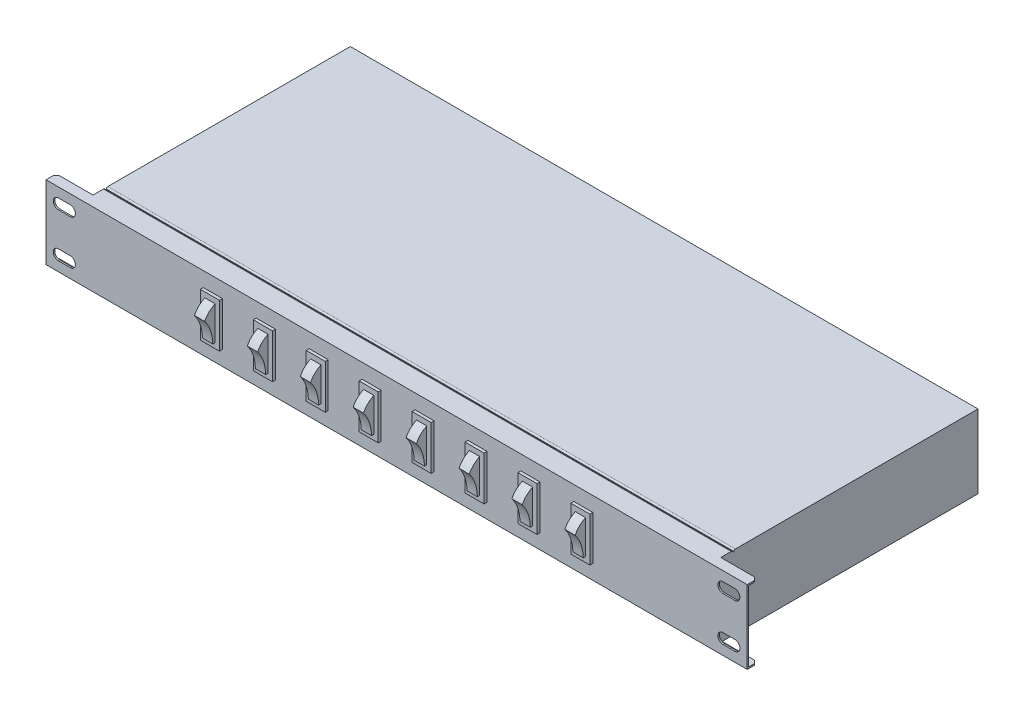
SolidWorks part; units mm, degrees
ref_plane "Front Plane" through (0, 0, 0) normal (0, 0, 1) x (1, 0, 0)
ref_plane "Top Plane" through (0, 0, 0) normal (0, 1, 0) x (1, 0, 0)
ref_plane "Right Plane" through (0, 0, 0) normal (1, 0, 0) x (0, 0, -1)
sketch "Sketch1" plane through (0, 0, 0) normal (0, 1, 0) x (1, 0, 0)
  line L1 (0, 0) -> (427, 0)
  line L2 (0, 0) -> (0, 182)
  line L3 (0, 182) -> (427, 182)
  line L4 (427, 0) -> (427, 182)
  dimension "D1" = 427
  dimension "D2" = 182
extrude "Boss-Extrude1" add sketch "Sketch1" along normal blind 50
sketch "Sketch2" plane through (0, 0, 0) normal (0, 0, 1) x (1, 0, 0)
  line L0 (18.7689, 0) -> (-75.6235, 0) construction
  line L1 (0, 0) -> (427, 0) construction
  line L2 (-16.5385, 40) -> (-8.5385, 40) construction
  line L3 (0, 50) -> (-25, 50)
  line L4 (0, 50) -> (0, 0)
  line L5 (0, 0) -> (-25, 0)
  line L6 (-25, 50) -> (-25, 0)
  line L7 (-16.5385, 43.5) -> (-8.5385, 43.5)
  line L8 (-16.5385, 36.5) -> (-8.5385, 36.5)
  line L9 (213.5, 50) -> (213.5, 0) construction
  line L10 (0, 50) -> (427, 50) construction
  line L11 (-25, 25) -> (0, 25) construction
  line L12 (-16.5385, 10) -> (-8.5385, 10) construction
  line L13 (-16.5385, 13.5) -> (-8.5385, 13.5)
  line L14 (-16.5385, 6.5) -> (-8.5385, 6.5)
  line L15 (427, 50) -> (452, 50)
  line L16 (427, 50) -> (427, 0)
  line L17 (452, 50) -> (452, 0)
  line L18 (427, 0) -> (452, 0)
  line L19 (443.5385, 10) -> (435.5385, 10) construction
  line L20 (443.5385, 6.5) -> (435.5385, 6.5)
  line L21 (443.5385, 13.5) -> (435.5385, 13.5)
  line L22 (443.5385, 40) -> (435.5385, 40) construction
  line L23 (443.5385, 36.5) -> (435.5385, 36.5)
  line L24 (443.5385, 43.5) -> (435.5385, 43.5)
  circle A0 centre (-16.5385, 40) radius 3.5
  circle A1 centre (-8.5385, 40) radius 3.5
  circle A2 centre (-8.5385, 10) radius 3.5
  circle A3 centre (-16.5385, 10) radius 3.5
  circle A4 centre (443.5385, 10) radius 3.5
  circle A5 centre (435.5385, 10) radius 3.5
  circle A6 centre (435.5385, 40) radius 3.5
  circle A7 centre (443.5385, 40) radius 3.5
  line M10 (427, 0) -> (427, 50)
  line M12 (0, 50) -> (0, 0)
  dimension "D3" = 10
  dimension "D1" = 25
  dimension "D2" = 8
extrude "Boss-Extrude2" add sketch "Sketch2" against normal blind 1 contours L3 L6 L5 A1 L8 A0 L7 L14 A3 L13 A2 M12 | L18 L17 L15 A5 L21 A4 L20 L24 A7 L23 A6 M10
sketch "Sketch3" plane through (0, 0, -1) normal (0, 0, -1) x (-1, 0, 0)
  line L0 (0, 50) -> (0, 0) construction
  line L1 (25, 0) -> (0, 0)
  line L2 (25, 0) -> (25, 1)
  line L3 (25, 1) -> (0, 1)
  line L4 (0, 0) -> (0, 1)
  line L5 (25, 50) -> (25, 0) construction
  line L6 (0, 50) -> (25, 50)
  line L7 (0, 50) -> (0, 49)
  line L8 (0, 49) -> (25, 49)
  line L9 (25, 50) -> (25, 49)
  line L10 (-452, 50) -> (-452, 0) construction
  line L11 (-427, 50) -> (-452, 50)
  line L12 (-427, 50) -> (-427, 49)
  line L13 (-427, 49) -> (-452, 49)
  line L14 (-452, 50) -> (-452, 49)
  line L16 (-427, 0) -> (-452, 0)
  line L17 (-427, 0) -> (-427, 1)
  line L18 (-427, 1) -> (-452, 1)
  line L19 (-452, 0) -> (-452, 1)
  dimension "D1" = 1
  dimension "D2" = 1
  dimension "D3" = 1
  dimension "D4" = 1
extrude "Boss-Extrude3" add sketch "Sketch3" along normal blind 6
chamfer "Chamfer1" distance 2 angle 45 4 edges at (-25, 0.5, -7) (-25, 49.5, -7) (452, 49.5, -7) (452, 0.5, -7)
sketch "Sketch4" plane through (0, 0, 0) normal (0, 0, 1) x (1, 0, 0)
  line L0 (-25, 0) -> (452, 0) construction
  line L1 (82, 40) -> (95, 40)
  line L2 (82, 40) -> (82, 10)
  line L3 (82, 10) -> (95, 10)
  line L4 (95, 40) -> (95, 10)
  line L5 (-25, 50) -> (-25, 0) construction
  line L6 (118, 10) -> (131, 10)
  line L7 (131, 40) -> (131, 10)
  line L8 (118, 40) -> (131, 40)
  line L9 (118, 40) -> (118, 10)
  line L10 (154, 10) -> (167, 10)
  line L11 (167, 40) -> (167, 10)
  line L12 (154, 40) -> (167, 40)
  line L13 (154, 40) -> (154, 10)
  line L14 (190, 10) -> (203, 10)
  line L15 (203, 40) -> (203, 10)
  line L16 (190, 40) -> (203, 40)
  line L17 (190, 40) -> (190, 10)
  line L18 (226, 10) -> (239, 10)
  line L19 (239, 40) -> (239, 10)
  line L20 (226, 40) -> (239, 40)
  line L21 (226, 40) -> (226, 10)
  line L22 (262, 10) -> (275, 10)
  line L23 (275, 40) -> (275, 10)
  line L24 (262, 40) -> (275, 40)
  line L25 (262, 40) -> (262, 10)
  line L26 (298, 10) -> (311, 10)
  line L27 (311, 40) -> (311, 10)
  line L28 (298, 40) -> (311, 40)
  line L29 (298, 40) -> (298, 10)
  line L30 (334, 10) -> (347, 10)
  line L31 (347, 40) -> (347, 10)
  line L32 (334, 40) -> (347, 40)
  line L33 (334, 40) -> (334, 10)
  dimension "D1" = 30
  dimension "D2" = 13
  dimension "D3" = 10
  dimension "D4" = 107
  dimension "D5" = 8
extrude "Boss-Extrude4" add sketch "Sketch4" along normal blind 2
sketch "Sketch5" plane through (0, 0, 2) normal (0, 0, 1) x (1, 0, 0)
  line L0 (88.5, 36.5) -> (88.5, 13.5) construction
  line L1 (85, 36.5) -> (92, 36.5)
  line L2 (85, 36.5) -> (85, 13.5)
  line L3 (85, 13.5) -> (92, 13.5)
  line L4 (92, 36.5) -> (92, 13.5)
  line L5 (82, 10) -> (95, 10) construction
  line L6 (82, 40) -> (82, 10) construction
  line L7 (128, 36.5) -> (128, 13.5)
  line L8 (121, 36.5) -> (121, 13.5)
  line L9 (121, 36.5) -> (128, 36.5)
  line L10 (121, 13.5) -> (128, 13.5)
  line L11 (164, 36.5) -> (164, 13.5)
  line L12 (157, 36.5) -> (157, 13.5)
  line L13 (157, 36.5) -> (164, 36.5)
  line L14 (157, 13.5) -> (164, 13.5)
  line L15 (200, 36.5) -> (200, 13.5)
  line L16 (193, 36.5) -> (193, 13.5)
  line L17 (193, 36.5) -> (200, 36.5)
  line L18 (193, 13.5) -> (200, 13.5)
  line L19 (236, 36.5) -> (236, 13.5)
  line L20 (229, 36.5) -> (229, 13.5)
  line L21 (229, 36.5) -> (236, 36.5)
  line L22 (229, 13.5) -> (236, 13.5)
  line L23 (272, 36.5) -> (272, 13.5)
  line L24 (265, 36.5) -> (265, 13.5)
  line L25 (265, 36.5) -> (272, 36.5)
  line L26 (265, 13.5) -> (272, 13.5)
  line L27 (308, 36.5) -> (308, 13.5)
  line L28 (301, 36.5) -> (301, 13.5)
  line L29 (301, 36.5) -> (308, 36.5)
  line L30 (301, 13.5) -> (308, 13.5)
  line L31 (344, 36.5) -> (344, 13.5)
  line L32 (337, 36.5) -> (337, 13.5)
  line L33 (337, 36.5) -> (344, 36.5)
  line L34 (337, 13.5) -> (344, 13.5)
  point P6 (88.5, 25)
  dimension "D1" = 7
  dimension "D2" = 23
  dimension "D3" = 15
  dimension "D4" = 6.5
  dimension "D5" = 8
extrude "Boss-Extrude5" add sketch "Sketch5" along normal blind 7
sketch "Sketch6" plane through (85, 0, 0) normal (-1, 0, 0) x (0, 0, 1)
  line L0 (9, 36.5) -> (9, 29.5) construction
  line L1 (9, 36.5) -> (9, 13.5) construction
  line L2 (2, 13.5) -> (3.5, 13.5)
  line L3 (9, 13.5) -> (2, 13.5) construction
  line L4 (2, 36.5) -> (2, 13.5)
  line L5 (9, 36.5) -> (9, 29.5)
  line L6 (2, 36.5) -> (9, 36.5)
  line L7 (3.5, 13.5) -> (9, 13.5)
  line L8 (9, 13.5) -> (9, 29.5)
  line L9 (9, 29.5) -> (8.9442, 29.6581)
  spline S0 degree 2 poles (2, 36.5) (7.2388, 33.7202) (9, 29.5) knots 0 0 0 0.496809 0.496809 0.496809
  spline S1 degree 2 poles (3.5, 13.5) (3.8992, 22.9335) (9, 29.5) knots 0 0 0 0.757593 0.757593 0.757593
  dimension "D1" = 7
  dimension "D2" = 1.5
extrude "Cut-Extrude1" cut sketch "Sketch6" against normal blind 267
sketch "Sketch7" plane through (0, 50, 0) normal (0, 1, 0) x (1, 0, 0)
  line L0 (0, 182) -> (0, 7) construction
  line L1 (0, 16) -> (427, 16)
  line L2 (0, 16) -> (0, 15)
  line L3 (0, 15) -> (427, 15)
  line L4 (427, 16) -> (427, 15)
  line L5 (427, 7) -> (427, 182) construction
  line L6 (-25, 0) -> (452, 0) construction
  dimension "D1" = 15
  dimension "D2" = 1
extrude "Cut-Extrude2" cut sketch "Sketch7" against normal blind 1
sketch "Sketch8" plane through (0, 0, 0) normal (0, -1, 0) x (1, 0, 0)
  line L0 (427, -7) -> (427, -182) construction
  line L1 (427, -16) -> (0, -16)
  line L2 (427, -16) -> (427, -15)
  line L3 (427, -15) -> (0, -15)
  line L4 (0, -16) -> (0, -15)
  line L5 (0, -182) -> (0, -7) construction
  line L6 (-25, 0) -> (452, 0) construction
  dimension "D1" = 15
  dimension "D2" = 1
extrude "Cut-Extrude3" cut sketch "Sketch8" against normal blind 1
fillet "Fillet1" radius 1 12 edges at (0, 49.5, -15) (0, 49.5, -16) (427, 49.5, -16) (427, 49.5, -15) (213.5, 50, -15) (213.5, 50, -16) (427, 0.5, -15) (427, 0.5, -16) (0, 0.5, -16) (0, 0.5, -15) (213.5, 0, -15) (213.5, 0, -16)
sketch "Sketch9" plane through (0, 0, -182) normal (0, 0, -1) x (-1, 0, 0)
  line L0 (-383, 25) -> (-354, 25) construction
  line L1 (-383, 38) -> (-354, 38)
  line L2 (-383, 38) -> (-383, 12)
  line L3 (-383, 12) -> (-354, 12)
  line L4 (-354, 38) -> (-354, 12)
  line L5 (-427, 0) -> (0, 0) construction
  line L6 (-427, 1) -> (-427, 49) construction
  line L7 (-343, 38) -> (-314, 38)
  line L8 (-343, 38) -> (-343, 12)
  line L9 (-343, 12) -> (-314, 12)
  line L10 (-314, 38) -> (-314, 12)
  line L11 (-303, 38) -> (-274, 38)
  line L12 (-303, 38) -> (-303, 12)
  line L13 (-303, 12) -> (-274, 12)
  line L14 (-274, 38) -> (-274, 12)
  line L15 (-263, 38) -> (-234, 38)
  line L16 (-263, 38) -> (-263, 12)
  line L17 (-263, 12) -> (-234, 12)
  line L18 (-234, 38) -> (-234, 12)
  line L19 (-223, 38) -> (-194, 38)
  line L20 (-223, 38) -> (-223, 12)
  line L21 (-223, 12) -> (-194, 12)
  line L22 (-194, 38) -> (-194, 12)
  line L23 (-183, 38) -> (-154, 38)
  line L24 (-183, 38) -> (-183, 12)
  line L25 (-183, 12) -> (-154, 12)
  line L26 (-154, 38) -> (-154, 12)
  line L27 (-143, 38) -> (-114, 38)
  line L28 (-143, 38) -> (-143, 12)
  line L29 (-143, 12) -> (-114, 12)
  line L30 (-114, 38) -> (-114, 12)
  line L31 (-103, 38) -> (-74, 38)
  line L32 (-103, 38) -> (-103, 12)
  line L33 (-103, 12) -> (-74, 12)
  line L34 (-74, 38) -> (-74, 12)
  dimension "D1" = 29
  dimension "D2" = 26
  dimension "D3" = 25
  dimension "D4" = 44
  dimension "D5" = 8
extrude "Boss-Extrude6" add sketch "Sketch9" along normal blind 4
sketch "Sketch10" plane through (0, 0, -186) normal (0, 0, -1) x (-1, 0, 0)
  line L0 (-375.6, 29.9) -> (-361.8648, 29.9) construction
  line L1 (-375.6, 33.075) -> (-374.1, 33.075)
  line L2 (-375.6, 33.075) -> (-375.6, 26.725)
  line L3 (-375.6, 26.725) -> (-374.1, 26.725)
  line L4 (-374.1, 33.075) -> (-374.1, 26.725)
  line L5 (-362.9, 33.075) -> (-361.4, 33.075)
  line L6 (-362.9, 33.075) -> (-362.9, 26.725)
  line L7 (-362.9, 26.725) -> (-361.4, 26.725)
  line L8 (-361.4, 33.075) -> (-361.4, 26.725)
  line L9 (-383, 12) -> (-354, 12) construction
  line L10 (-383, 38) -> (-383, 12) construction
  line L11 (-322.9, 33.075) -> (-322.9, 26.725)
  line L12 (-322.9, 33.075) -> (-321.4, 33.075)
  line L13 (-321.4, 33.075) -> (-321.4, 26.725)
  line L14 (-322.9, 26.725) -> (-321.4, 26.725)
  line L15 (-335.6, 26.725) -> (-334.1, 26.725)
  line L16 (-334.1, 33.075) -> (-334.1, 26.725)
  line L17 (-335.6, 33.075) -> (-335.6, 26.725)
  line L18 (-335.6, 33.075) -> (-334.1, 33.075)
  line L19 (-282.9, 33.075) -> (-282.9, 26.725)
  line L20 (-282.9, 33.075) -> (-281.4, 33.075)
  line L21 (-281.4, 33.075) -> (-281.4, 26.725)
  line L22 (-282.9, 26.725) -> (-281.4, 26.725)
  line L23 (-295.6, 26.725) -> (-294.1, 26.725)
  line L24 (-294.1, 33.075) -> (-294.1, 26.725)
  line L25 (-295.6, 33.075) -> (-295.6, 26.725)
  line L26 (-295.6, 33.075) -> (-294.1, 33.075)
  line L27 (-242.9, 33.075) -> (-242.9, 26.725)
  line L28 (-242.9, 33.075) -> (-241.4, 33.075)
  line L29 (-241.4, 33.075) -> (-241.4, 26.725)
  line L30 (-242.9, 26.725) -> (-241.4, 26.725)
  line L31 (-255.6, 26.725) -> (-254.1, 26.725)
  line L32 (-254.1, 33.075) -> (-254.1, 26.725)
  line L33 (-255.6, 33.075) -> (-255.6, 26.725)
  line L34 (-255.6, 33.075) -> (-254.1, 33.075)
  line L35 (-202.9, 33.075) -> (-202.9, 26.725)
  line L36 (-202.9, 33.075) -> (-201.4, 33.075)
  line L37 (-201.4, 33.075) -> (-201.4, 26.725)
  line L38 (-202.9, 26.725) -> (-201.4, 26.725)
  line L39 (-215.6, 26.725) -> (-214.1, 26.725)
  line L40 (-214.1, 33.075) -> (-214.1, 26.725)
  line L41 (-215.6, 33.075) -> (-215.6, 26.725)
  line L42 (-215.6, 33.075) -> (-214.1, 33.075)
  line L43 (-162.9, 33.075) -> (-162.9, 26.725)
  line L44 (-162.9, 33.075) -> (-161.4, 33.075)
  line L45 (-161.4, 33.075) -> (-161.4, 26.725)
  line L46 (-162.9, 26.725) -> (-161.4, 26.725)
  line L47 (-175.6, 26.725) -> (-174.1, 26.725)
  line L48 (-174.1, 33.075) -> (-174.1, 26.725)
  line L49 (-175.6, 33.075) -> (-175.6, 26.725)
  line L50 (-175.6, 33.075) -> (-174.1, 33.075)
  line L51 (-122.9, 33.075) -> (-122.9, 26.725)
  line L52 (-122.9, 33.075) -> (-121.4, 33.075)
  line L53 (-121.4, 33.075) -> (-121.4, 26.725)
  line L54 (-122.9, 26.725) -> (-121.4, 26.725)
  line L55 (-135.6, 26.725) -> (-134.1, 26.725)
  line L56 (-134.1, 33.075) -> (-134.1, 26.725)
  line L57 (-135.6, 33.075) -> (-135.6, 26.725)
  line L58 (-135.6, 33.075) -> (-134.1, 33.075)
  line L59 (-82.9, 33.075) -> (-82.9, 26.725)
  line L60 (-82.9, 33.075) -> (-81.4, 33.075)
  line L61 (-81.4, 33.075) -> (-81.4, 26.725)
  line L62 (-82.9, 26.725) -> (-81.4, 26.725)
  line L63 (-95.6, 26.725) -> (-94.1, 26.725)
  line L64 (-94.1, 33.075) -> (-94.1, 26.725)
  line L65 (-95.6, 33.075) -> (-95.6, 26.725)
  line L66 (-95.6, 33.075) -> (-94.1, 33.075)
  circle A0 centre (-368.5, 18) radius 2.375
  circle A1 centre (-328.5, 18) radius 2.375
  circle A2 centre (-288.5, 18) radius 2.375
  circle A3 centre (-248.5, 18) radius 2.375
  circle A4 centre (-208.5, 18) radius 2.375
  circle A5 centre (-168.5, 18) radius 2.375
  circle A6 centre (-128.5, 18) radius 2.375
  circle A7 centre (-88.5, 18) radius 2.375
  point P12 (-362.9, 29.9)
  point P17 (-374.85, 33.075)
  point P18 (-362.15, 33.075)
  dimension "D1" = 4.75
  dimension "D2" = 6.35
  dimension "D3" = 6.35
  dimension "D4" = 1.5
  dimension "D5" = 1.5
  dimension "D6" = 11.9
  dimension "D7" = 0
  dimension "D8" = 6
  dimension "D9" = 14.5
  dimension "D10" = 12.7
  dimension "D11" = 6.35
  dimension "D12" = 8
extrude "Cut-Extrude4" cut sketch "Sketch10" against normal blind 15
chamfer "Chamfer2" distance 1 angle 45 72 edges at (362.9, 29.9, -186) (362.15, 33.075, -186) (361.4, 29.9, -186) (362.15, 26.725, -186) (374.85, 26.725, -186) (375.6, 29.9, -186) (374.85, 33.075, -186) (374.1, 29.9, -186) (366.125, 18, -186) (94.85, 26.725, -186) (94.1, 29.9, -186) (94.85, 33.075, -186) (95.6, 29.9, -186) (81.4, 29.9, -186) (82.15, 26.725, -186) (82.9, 29.9, -186) (82.15, 33.075, -186) (122.15, 26.725, -186) (121.4, 29.9, -186) (122.15, 33.075, -186) (122.9, 29.9, -186) (134.85, 26.725, -186) (134.1, 29.9, -186) (134.85, 33.075, -186) (135.6, 29.9, -186) (162.15, 26.725, -186) (161.4, 29.9, -186) (162.15, 33.075, -186) (162.9, 29.9, -186) (174.85, 26.725, -186) (174.1, 29.9, -186) (175.6, 29.9, -186) (174.85, 33.075, -186) (86.125, 18, -186) (126.125, 18, -186) (166.125, 18, -186) (206.125, 18, -186) (202.15, 26.725, -186) (201.4, 29.9, -186) (202.15, 33.075, -186) (202.9, 29.9, -186) (215.6, 29.9, -186) (214.85, 33.075, -186) (214.1, 29.9, -186) (214.85, 26.725, -186) (246.125, 18, -186) (242.15, 26.725, -186) (241.4, 29.9, -186) (242.15, 33.075, -186) (242.9, 29.9, -186) (255.6, 29.9, -186) (254.85, 33.075, -186) (254.1, 29.9, -186) (254.85, 26.725, -186) (282.15, 26.725, -186) (281.4, 29.9, -186) (282.15, 33.075, -186) (282.9, 29.9, -186) (286.125, 18, -186) (294.1, 29.9, -186) (294.85, 26.725, -186) (295.6, 29.9, -186) (294.85, 33.075, -186) (335.6, 29.9, -186) (334.85, 33.075, -186) (334.1, 29.9, -186) (334.85, 26.725, -186) (322.15, 26.725, -186) (321.4, 29.9, -186) (322.15, 33.075, -186) (322.9, 29.9, -186) (326.125, 18, -186)
sketch "Sketch11" plane through (0, 0, -182) normal (0, 0, -1) x (-1, 0, 0)
  line L0 (-427, 0) -> (0, 0) construction
  line L1 (-17.5363, 40.5) -> (-42.5363, 40.5)
  line L2 (-15.5363, 38.5) -> (-15.5363, 11.5)
  line L3 (-17.5363, 9.5) -> (-42.5363, 9.5)
  line L4 (-44.5363, 38.5) -> (-44.5363, 11.5)
  arc A0 (-17.5363, 40.5) -> (-15.5363, 38.5) centre (-17.5363, 38.5) cw
  arc A1 (-15.5363, 11.5) -> (-17.5363, 9.5) centre (-17.5363, 11.5) cw
  arc A2 (-42.5363, 9.5) -> (-44.5363, 11.5) centre (-42.5363, 11.5) cw
  arc A3 (-44.5363, 38.5) -> (-42.5363, 40.5) centre (-42.5363, 38.5) cw
  point P10 (-15.5363, 9.5)
  point P13 (-44.5363, 9.5)
  point P16 (-44.5363, 40.5)
  dimension "D4" = 2
  dimension "D1" = 29
  dimension "D2" = 31
  dimension "D3" = 9.5
extrude "Boss-Extrude7" add sketch "Sketch11" along normal blind 3.5
sketch "Sketch12" plane through (0, 0, -185.5) normal (0, 0, -1) x (-1, 0, 0)
  line L8 (-17.5363, 39.5) -> (-42.5363, 39.5)
  line L9 (-43.5363, 38.5) -> (-43.5363, 11.5)
  line L10 (-42.5363, 10.5) -> (-17.5363, 10.5)
  line L11 (-16.5363, 11.5) -> (-16.5363, 38.5)
  line L12 (-17.5363, 39.5) -> (-42.5363, 39.5)
  line L13 (-43.5363, 38.5) -> (-43.5363, 11.5)
  line L14 (-42.5363, 10.5) -> (-17.5363, 10.5)
  line L15 (-16.5363, 11.5) -> (-16.5363, 38.5)
  arc A8 (-16.5363, 38.5) -> (-17.5363, 39.5) centre (-17.5363, 38.5) ccw
  arc A9 (-42.5363, 39.5) -> (-43.5363, 38.5) centre (-42.5363, 38.5) ccw
  arc A10 (-43.5363, 11.5) -> (-42.5363, 10.5) centre (-42.5363, 11.5) ccw
  arc A11 (-17.5363, 10.5) -> (-16.5363, 11.5) centre (-17.5363, 11.5) ccw
  arc A12 (-16.5363, 38.5) -> (-17.5363, 39.5) centre (-17.5363, 38.5) ccw
  arc A13 (-42.5363, 39.5) -> (-43.5363, 38.5) centre (-42.5363, 38.5) ccw
  arc A14 (-43.5363, 11.5) -> (-42.5363, 10.5) centre (-42.5363, 11.5) ccw
  arc A15 (-17.5363, 10.5) -> (-16.5363, 11.5) centre (-17.5363, 11.5) ccw
  dimension "D1" = 1
extrude "Boss-Extrude8" add sketch "Sketch12" along normal blind 1.5
sketch "Sketch13" plane through (0, 0, -187) normal (0, 0, -1) x (-1, 0, 0)
  line L0 (-43.5363, 38.5) -> (-43.5363, 11.5) construction
  line L1 (-42.0363, 21.5) -> (-18.0363, 21.5)
  line L2 (-42.0363, 21.5) -> (-42.0363, 33.5)
  line L3 (-42.0363, 33.5) -> (-18.0363, 33.5)
  line L4 (-18.0363, 21.5) -> (-18.0363, 33.5)
  line L5 (-42.0363, 33.5) -> (-38.0363, 37.5)
  line L6 (-38.0363, 33.5) -> (-22.0363, 33.5)
  line L7 (-38.0363, 33.5) -> (-38.0363, 37.5)
  line L8 (-38.0363, 37.5) -> (-22.0363, 37.5)
  line L9 (-22.0363, 33.5) -> (-22.0363, 37.5)
  line L10 (-22.0363, 37.5) -> (-18.0363, 33.5)
  line L11 (-17.5363, 39.5) -> (-42.5363, 39.5) construction
  dimension "D1" = 24
  dimension "D2" = 1.5
  dimension "D3" = 12
  dimension "D4" = 4
  dimension "D5" = 4
  dimension "D6" = 16
  dimension "D7" = 2
extrude "Cut-Extrude5" cut sketch "Sketch13" against normal blind 15 contours L1 L4 L3 L2 | L3 L7 L5 | L3 L9 L8 L7 | L10 L9 L3
sketch "Sketch14" plane through (0, 0, -172) normal (0, 0, -1) x (-1, 0, 0)
  line L0 (-36.5363, 27.69) -> (-23.0363, 27.69) construction
  line L1 (-38.0363, 29.19) -> (-36.5363, 29.19)
  line L2 (-38.0363, 29.19) -> (-38.0363, 26.19)
  line L3 (-38.0363, 26.19) -> (-36.5363, 26.19)
  line L4 (-36.5363, 29.19) -> (-36.5363, 26.19)
  line L5 (-23.0363, 29.19) -> (-21.5363, 29.19)
  line L6 (-23.0363, 29.19) -> (-23.0363, 26.19)
  line L7 (-23.0363, 26.19) -> (-21.5363, 26.19)
  line L8 (-21.5363, 29.19) -> (-21.5363, 26.19)
  line L9 (-30.7863, 34.19) -> (-29.2863, 34.19)
  line L10 (-30.7863, 34.19) -> (-30.7863, 31.19)
  line L11 (-30.7863, 31.19) -> (-29.2863, 31.19)
  line L12 (-29.2863, 34.19) -> (-29.2863, 31.19)
  line L13 (-42.0363, 21.5) -> (-42.0363, 33.5) construction
  point P14 (-30.7863, 32.69)
  point P15 (-37.2863, 29.19)
  point P16 (-22.2863, 29.19)
  point P19 (-30.0363, 34.19)
  dimension "D1" = 1.5
  dimension "D2" = 1.5
  dimension "D3" = 1.5
  dimension "D4" = 5
  dimension "D5" = 15
  dimension "D6" = 4
  dimension "D7" = 12
  dimension "D8" = 3
  dimension "D9" = 3
extrude "Boss-Extrude9" add sketch "Sketch14" along normal blind 14
chamfer "Chamfer3" distance 0.75 angle 45 6 edges at (22.2863, 26.19, -186) (37.2863, 26.19, -186) (22.2863, 29.19, -186) (37.2863, 29.19, -186) (30.0363, 31.19, -186) (30.0363, 34.19, -186)
sketch "Sketch15" plane through (0, 0, -187) normal (0, 0, -1) x (-1, 0, 0)
  line L0 (-42.0363, 21.5) -> (-42.0363, 33.5) construction
  line L1 (-42.0363, 20) -> (-18.0363, 20)
  line L2 (-42.0363, 20) -> (-42.0363, 12)
  line L3 (-42.0363, 12) -> (-18.0363, 12)
  line L4 (-18.0363, 20) -> (-18.0363, 12)
  line L5 (-42.0363, 21.5) -> (-18.0363, 21.5) construction
  line L6 (-42.5363, 10.5) -> (-17.5363, 10.5) construction
  line L7 (-41.5363, 19.5) -> (-41.5363, 12.5)
  line L8 (-41.5363, 12.5) -> (-18.5363, 12.5)
  line L9 (-18.5363, 19.5) -> (-18.5363, 12.5)
  line L10 (-41.5363, 19.5) -> (-18.5363, 19.5)
  dimension "D1" = 0
  dimension "D2" = 24
  dimension "D3" = 1.5
  dimension "D4" = 1.5
  dimension "D5" = 0.5
extrude "Cut-Extrude6" cut sketch "Sketch15" against normal blind 0.5
